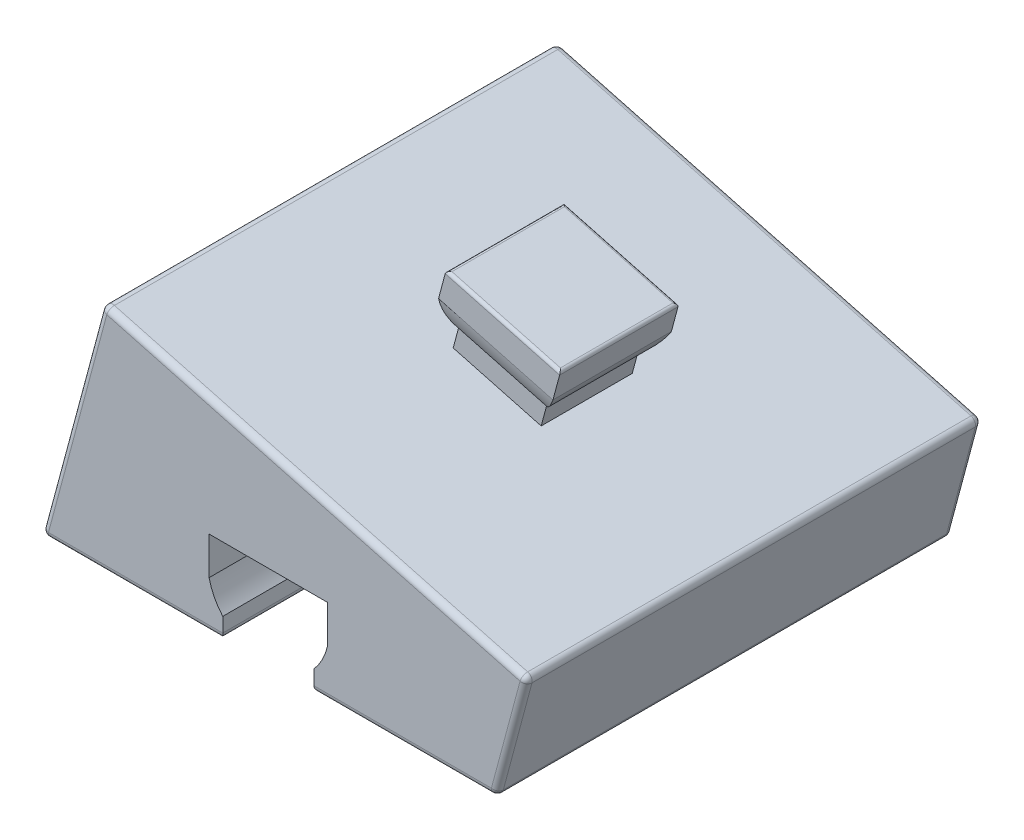
SolidWorks part; units mm, degrees
ref_plane "前视基准面" through (0, 0, 0) normal (0, 0, 1) x (1, 0, 0)
ref_plane "上视基准面" through (0, 0, 0) normal (0, 1, 0) x (1, 0, 0)
ref_plane "右视基准面" through (0, 0, 0) normal (1, 0, 0) x (0, 0, -1)
sketch "草图1" plane through (0, 0, 0) normal (0, 0, 1) x (1, 0, 0)
  line L0 (-7.5, 0) -> (-1.5, 0)
  line L1 (7.5, 0) -> (8.5353, 3.8637)
  line L2 (-7.5, 0) -> (-5.4599, 7.6137)
  line L3 (8.5353, 3.8637) -> (-5.4599, 7.6137)
  line L4 (-1.5, 0) -> (-1.5, 0.6771)
  line L5 (1.5, 0.6771) -> (1.5, 0)
  line L6 (1.5, 0) -> (7.5, 0)
  line L7 (-1.95, 2.8) -> (1.95, 2.8)
  line L8 (-1.95, 2.8) -> (-1.95, 1.5556)
  line L9 (1.95, 2.8) -> (1.95, 1.5556)
  arc A0 (1.5, 0.6771) -> (1.95, 1.5556) centre (0, 2) ccw
  arc A1 (-1.95, 1.5556) -> (-1.5, 0.6771) centre (0, 2) ccw
extrude "凸台-拉伸1" add sketch "草图1" along normal blind 7.5 and the other way blind 7.5
sketch "草图2" plane through (0, 0, 0) normal (0, 0, 1) x (1, 0, 0)
  line L0 (0.0888, 6.1269) -> (2.9866, 5.3505)
  line L1 (8.5353, 3.8637) -> (-5.4599, 7.6137) construction
  line L2 (2.9866, 5.3505) -> (3.2454, 6.3164)
  line L3 (3.2454, 6.3164) -> (0.3476, 7.0929)
  line L4 (0.3476, 7.0929) -> (0.0888, 6.1269)
extrude "凸台-拉伸2" add sketch "草图2" along normal blind 1.5 and the other way blind 1.5
sketch "草图3" plane through (0, 0, 0) normal (0, 0, 1) x (1, 0, 0)
  line L3 (2.1847, 8.1535) -> (4.0683, 7.6488)
  line L4 (2.1847, 8.1535) -> (0.3012, 8.6582)
  line L5 (0.3012, 8.6582) -> (0.0567, 7.746)
  line L7 (4.0683, 7.6488) -> (3.8239, 6.7366)
  line L9 (0.3476, 7.0929) -> (0.0888, 6.1269) construction
  line L10 (0.264, 6.781) -> (3.1618, 6.0045)
  arc A0 (3.1618, 6.0045) -> (3.8239, 6.7366) centre (2.0553, 7.6706) ccw
  arc A2 (0.0567, 7.746) -> (0.264, 6.781) centre (2.0553, 7.6706) ccw
extrude "凸台-拉伸3" add sketch "草图3" along normal blind 2 and the other way blind 2
sketch "草图4" plane through (-1.8836, 0.5047, 0) normal (-0.9659, 0.2588, 0) x (0, 0, 1)
  line L1 (1.95, 8.4411) -> (2, 8.4411)
  line L2 (-2, 8.4411) -> (2, 8.4411) construction
  line L3 (1.95, 8.4411) -> (1.95, 7.4967)
  line L5 (1.5, 6.6183) -> (2, 6.6183)
  line L6 (-1.95, 8.4411) -> (-1.95, 7.4967)
  line L7 (-2, 8.4411) -> (-1.95, 8.4411)
  line L9 (-2, 8.4411) -> (-2, 6.6183)
  line L10 (-2, 6.6183) -> (-1.5, 6.6183)
  line L11 (2, 8.4411) -> (2, 6.6183)
  arc A0 (1.5, 6.6183) -> (1.95, 7.4967) centre (0, 7.9411) ccw
  arc A1 (-1.95, 7.4967) -> (-1.5, 6.6183) centre (0, 7.9411) ccw
extrude "切除-拉伸1" cut sketch "草图4" against normal through all
fillet "圆角1" radius 0.2 16 edges at (4.5, 0, -7.5) (1.5, 0, 0) (4.5, 0, 7.5) (-4.5, 0, -7.5) (-4.5, 0, 7.5) (-1.5, 0, 0) (-6.48, 3.8069, -7.5) (-5.4599, 7.6137, 0) (-6.48, 3.8069, 7.5) (-7.5, 0, 0) (8.0176, 1.9319, -7.5) (7.5, 0, 0) (8.0176, 1.9319, 7.5) (8.5353, 3.8637, 0) (1.5377, 5.7387, -7.5) (1.5377, 5.7387, 7.5)
fillet "圆角2" radius 0.1 4 edges at (4.0683, 7.6488, 0) (2.1847, 8.1535, 1.95) (0.3012, 8.6582, 0) (2.1847, 8.1535, -1.95)
